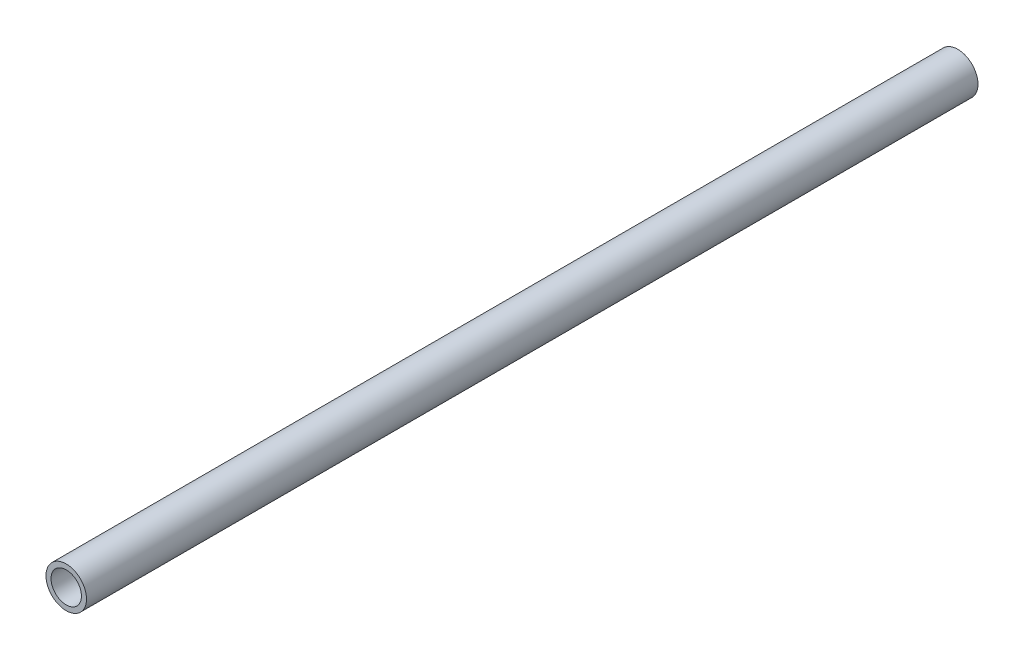
SolidWorks part; units mm, degrees
material "PC High Viscosity"
ref_plane "Front Plane" through (0, 0, 0) normal (0, 0, 1) x (1, 0, 0)
ref_plane "Top Plane" through (0, 0, 0) normal (0, 1, 0) x (1, 0, 0)
ref_plane "Right Plane" through (0, 0, 0) normal (1, 0, 0) x (0, 0, -1)
sketch "Sketch2" plane through (0, 0, 0) normal (0, 0, 1) x (1, 0, 0)
  circle A0 centre (0, 0) radius 9.525
  circle A1 centre (0, 0) radius 12.7
  dimension "D1" = 25.4
  dimension "D2" = 19.05
extrude "Boss-Extrude1" add sketch "Sketch2" along normal mid plane 558.8
